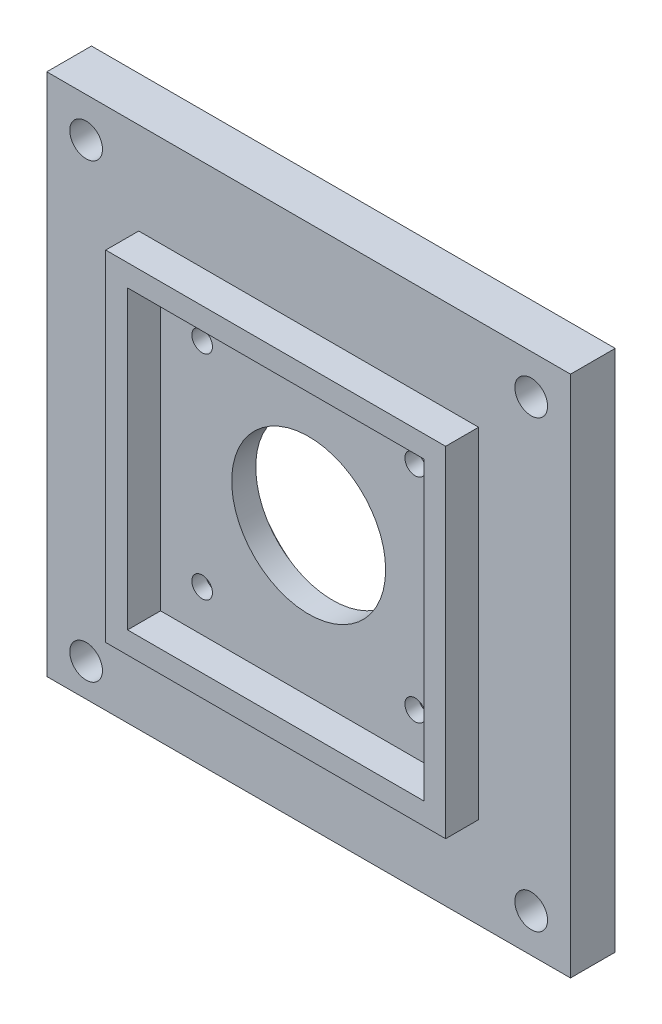
SolidWorks part; units mm, degrees
material "Pure Gold"
ref_plane "Front" through (0, 0, 0) normal (0, 0, 1) x (1, 0, 0)
ref_plane "Top" through (0, 0, 0) normal (0, 1, 0) x (1, 0, 0)
ref_plane "Right" through (0, 0, 0) normal (1, 0, 0) x (0, 0, -1)
sketch "Sketch4" plane through (0, 0, 0) normal (0, 0, 1) x (1, 0, 0)
  line L0 (0, -42.8625) -> (0, 41.275) construction
  line L1 (-49.15, -15.5) -> (-80.15, 15.5) construction
  line L2 (-80.15, -15.5) -> (-49.15, 15.5) construction
  line L3 (-39.925, 44.5615) -> (-39.925, -66.5635) construction
  line L4 (-71.275, 44.5615) -> (-71.275, -66.5635) construction
  line L8 (-62.05, 15.5) -> (-31.05, -15.5) construction
  line L9 (-31.05, 15.5) -> (-62.05, -15.5) construction
  line L11 (-31.05, 36.624) -> (-31.05, -53.8635) construction
  line L12 (43.75, 0) -> (-164.4633, 0) construction
  line L13 (-62.05, 36.624) -> (-62.05, -53.8635) construction
  line L14 (-49.15, 36.624) -> (-49.15, -53.8635) construction
  line L15 (-80.15, 36.624) -> (-80.15, -53.8635) construction
  line L16 (-113.2228, 15.5) -> (-0.2036, 15.5) construction
  line L17 (-113.2228, -15.5) -> (-0.2036, -15.5) construction
  line L18 (-25, -66.5635) -> (-25, 44.5615) construction
  line L19 (-68.1, -66.5635) -> (-68.1, 44.5615) construction
  line L20 (-43.1, 44.5615) -> (-43.1, -66.5635) construction
  line L21 (-86.2, -66.5635) -> (-86.2, 44.5615) construction
  line L22 (5.8397, -21.55) -> (-134.1626, -21.55) construction
  line L23 (5.8397, 21.55) -> (-134.1626, 21.55) construction
  line L24 (10.9249, -24.725) -> (-138.6228, -24.725) construction
  line L25 (10.9249, 24.725) -> (-138.6228, 24.725) construction
  line L26 (-89.375, 44.5615) -> (-89.375, -66.5635) construction
  line L27 (-21.825, 44.5615) -> (-21.825, -66.5635) construction
  circle A0 centre (0, 0) radius 12.7 construction
  circle A1 centre (0, 0) radius 15.875 construction
  circle A2 centre (0, 0) radius 9.46 construction
  circle A3 centre (-93.65, 0) radius 9.46 construction
  arc A4 (-93.65, 12.7) -> (-93.65, -12.7) centre (-93.65, 0) ccw construction
  circle A5 centre (27.27, 0) radius 9.46 construction
  circle A6 centre (27.27, 0) radius 12.7 construction
  circle A7 centre (-120.3675, 0) radius 9.46 construction
  circle A8 centre (-120.3675, 0) radius 12.7 construction
  point P3 (0, 0)
  point P6 (-49.15, -15.5)
  point P11 (-93.65, 0)
  point P12 (-49.15, 15.5)
  point P13 (-46.55, 0)
  point P14 (-80.15, 15.5)
  point P15 (-80.15, -15.5)
  point P61 (-64.65, 0)
  point P65 (27.27, 0)
  point P66 (-120.3675, 0)
  dimension "D20" = 3.175
  dimension "D18" = 29
  dimension "D26" = 73.82
  dimension "D27" = 64.65
  dimension "D2" = 31
  dimension "D3" = 25
  dimension "D4" = 31
  dimension "D5" = 21.825
  dimension "D6" = 15.5
  dimension "D7" = 15.5
  dimension "D8" = 6.05
  dimension "D9" = 6.05
  dimension "D10" = 6.05
  dimension "D11" = 6.05
  dimension "D12" = 6.05
  dimension "D13" = 6.05
  dimension "D14" = 3.175
  dimension "D15" = 3.175
  dimension "D16" = 3.175
  dimension "D17" = 3.175
  dimension "D19" = 3.175
  dimension "D21" = 3.175
  dimension "D22" = 46.55
  dimension "D23" = 47.1
  dimension "D24" = 58.32
  dimension "D25" = 147.6375
sketch "Sketch5" plane through (0, 0, 0) normal (0, 0, 1) x (1, 0, 0)
  line L0 (-25, -21.55) -> (-25, 21.55)
  line L1 (-25, -66.5635) -> (-25, 44.5615) construction
  line L2 (5.8397, -21.55) -> (-134.1626, -21.55) construction
  line L3 (5.8397, 21.55) -> (-134.1626, 21.55) construction
  line L4 (-25, 21.55) -> (-68.1, 21.55)
  line L6 (-68.1, -66.5635) -> (-68.1, 44.5615) construction
  line L7 (-68.1, 21.55) -> (-68.1, -21.55)
  line L8 (-68.1, -21.55) -> (-25, -21.55)
  line L9 (-21.825, 24.725) -> (-21.825, -24.725)
  line L10 (10.9249, 24.725) -> (-138.6228, 24.725) construction
  line L11 (-21.825, 44.5615) -> (-21.825, -66.5635) construction
  line L12 (10.9249, -24.725) -> (-138.6228, -24.725) construction
  line L13 (-21.825, -24.725) -> (-71.275, -24.725)
  line L14 (-71.275, 44.5615) -> (-71.275, -66.5635) construction
  line L15 (-71.275, -24.725) -> (-71.275, 24.725)
  line L16 (-71.275, 24.725) -> (-21.825, 24.725)
extrude "Extrude1" add sketch "Sketch5" along normal blind 4.8
sketch "Sketch6" plane through (0, 0, 0) normal (0, 0, -1) x (-1, 0, 0)
  line L0 (8.45, 83.4705) -> (8.45, -75.5808) construction
  line L1 (84.65, 274.6375) -> (84.65, -282.0493) construction
  line L2 (409.575, -38.1) -> (-293.1783, -38.1) construction
  line L3 (387.35, 38.1) -> (-330.5618, 38.1) construction
  line L4 (8.45, 38.1) -> (8.45, -37.987)
  line L5 (8.45, -37.987) -> (84.65, -38.1)
  line L6 (84.65, -38.1) -> (84.65, 38.1)
  line L7 (84.65, 38.1) -> (8.45, 38.1)
  line L8 (14.17, 92.075) -> (14.17, -77.5708) construction
  line L9 (78.93, 88.9) -> (78.93, -84.1375) construction
  line L10 (-44.45, 32.38) -> (120.65, 32.38) construction
  line L11 (-14.2875, -32.38) -> (123.825, -32.38) construction
  circle A0 centre (62.05, 15.5) radius 1.5
  circle A1 centre (31.05, 15.5) radius 1.5
  circle A2 centre (62.05, -15.5) radius 1.5
  circle A3 centre (31.05, -15.5) radius 1.5
  circle A4 centre (14.17, 32.38) radius 2.3812
  circle A5 centre (78.93, 32.38) radius 2.3813
  circle A6 centre (78.93, -33.3094) radius 2.3813
  circle A7 centre (14.17, -32.38) radius 2.3812
  circle A8 centre (46.55, 0) radius 11.2
  dimension "D1" = 38.1
  dimension "D9" = 64.76
  dimension "D2" = 76.2
  dimension "D3" = 38.1
  dimension "D4" = 76.2
  dimension "D5" = 5.72
  dimension "D6" = 5.72
  dimension "D7" = 5.72
  dimension "D8" = 5.72
extrude "Extrude2" add sketch "Sketch6" along normal blind 6.5
sketch "Sketch7" plane through (0, 0, -6.5) normal (0, 0, -1) x (-1, 0, 0)
  circle A2 centre (62.05, -15.5) radius 6
  circle A3 centre (31.05, -15.5) radius 6
extrude "Extrude3" cut sketch "Sketch7" against normal blind 4.5
sketch "Sketch8" plane through (0, 0, -6.5) normal (0, 0, -1) x (-1, 0, 0)
  circle A0 centre (62.05, 15.5) radius 6
  circle A1 centre (31.05, 15.5) radius 6
extrude "Extrude4" cut sketch "Sketch8" against normal blind 3.5
sketch "Sketch9" plane through (0, 0, -6.5) normal (0, 0, -1) x (-1, 0, 0)
  line L0 (31.05, 15.5) -> (62.05, -15.5) construction
  line L1 (31.05, -15.5) -> (62.05, 15.5) construction
  line L2 (22.225, 10) -> (71.4375, 10) construction
  line L3 (22.225, -10) -> (71.4375, -10) construction
  line L4 (36.55, 23.8125) -> (36.55, -23.8125) construction
  line L5 (56.55, 23.8125) -> (56.55, -25.4) construction
  circle A0 centre (46.55, 0) radius 15.3625
  dimension "D1" = 10
  dimension "D2" = 10
  dimension "D3" = 10
  dimension "D4" = 10
extrude "Extrude5" cut sketch "Sketch9" against normal blind 3
